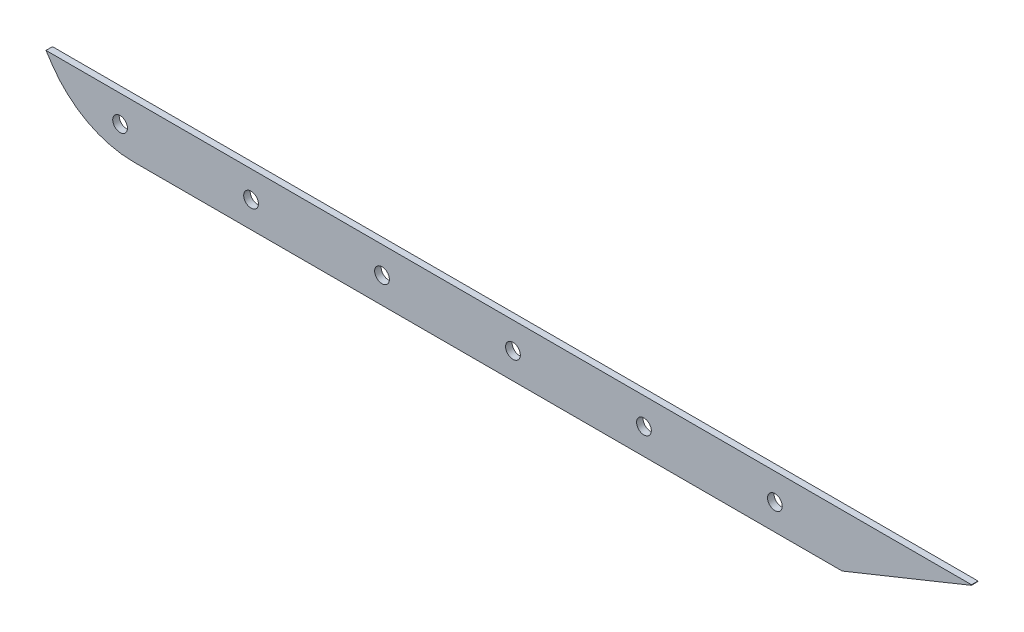
SolidWorks part; units mm, degrees
material "5052-H34"
ref_plane "Front Plane" through (0, 0, 0) normal (0, 0, 1) x (1, 0, 0)
ref_plane "Top Plane" through (0, 0, 0) normal (0, 1, 0) x (1, 0, 0)
ref_plane "Right Plane" through (0, 0, 0) normal (1, 0, 0) x (0, 0, -1)
sketch "Sketch1" plane through (0, 0, 0) normal (0, 0, 1) x (1, 0, 0)
  line L3 (428.1206, 28.9396) -> (0.5404, 28.9396)
  line L6 (-98.8794, 3.851) -> (-31.8794, -96.649)
  line L7 (428.1206, 28.9396) -> (403.1206, -71.149)
  line L9 (403.1206, -71.149) -> (366, -96.649)
  line L10 (-31.8794, -96.649) -> (366, -96.649)
  line L11 (0.5404, 28.9396) -> (-115.6052, 28.9396)
  line L12 (-98.8794, 3.851) -> (-115.6052, 28.9396)
  line L13 (-49.0861, -70.839) -> (403.198, -70.839)
  circle A0 centre (-12.8794, -83.899) radius 3.6
  circle A1 centre (51.1206, -83.899) radius 3.6
  circle A2 centre (115.1206, -83.899) radius 3.6
  circle A3 centre (179.1206, -83.899) radius 3.6
  circle A4 centre (243.1206, -83.899) radius 3.6
  circle A5 centre (307.1206, -83.899) radius 3.6
  point P0 (-48.8794, -71.149)
  point P2 (-31.8794, -96.649)
  point P8 (48, -83.899)
  point P9 (403.1206, -71.149)
  point P23 (-49.0861, -70.839)
  point P26 (403.198, -70.839)
  dimension "D2" = 64
  dimension "D4" = 64
  dimension "D1" = 25.5
  dimension "D3" = 75
  dimension "D5" = 25
  dimension "D6" = 96
  dimension "D7" = 527
  dimension "D8" = 180
  dimension "D9" = 64
  dimension "D10" = 64
  dimension "D11" = 64
  dimension "D12" = 123.69
  dimension "D13" = 12.75
  dimension "D14" = 25.81
  dimension "D15" = 25.81
extrude "Boss-Extrude1" add sketch "Sketch1" along normal blind 3.175 contours L3 L11 L12 L6 L10 L9 L7
extrude "Cut-Extrude1" cut sketch "Sketch1<4>" along normal through all contours A0 | A1 | A2 | A3 | A4 | A5 region at (-12.8794, -83.899, 0)
sketch "Sketch1<4>" plane through (0, 0, 0) normal (0, 0, 1) x (1, 0, 0) same geometry as "Sketch1"
sketch "Sketch2" plane through (0, 0, 0) normal (0, 0, -1) x (-1, 0, 0)
  circle A0 centre (-275.1206, -83.899) radius 6.5
  circle A2 centre (-233.5603, -132.5687) radius 6.5
  circle A3 centre (-192, -83.899) radius 6.5
  circle A4 centre (-128, -83.899) radius 6.5
  circle A5 centre (-64, -83.899) radius 6.5
  circle A6 centre (0, -83.899) radius 6.5
  dimension "D2" = 0
  dimension "D3" = 64
  dimension "D4" = 64
  dimension "D5" = 64
  dimension "D6" = 64
  dimension "D7" = 64
  dimension "D1" = 32
sketch "Sketch5" plane through (0, 0, 0) normal (0, 0, -1) x (-1, 0, 0)
  line L0 (48.8794, -71.149) -> (-14.2353, -96.649)
  line L1 (31.8794, -96.649) -> (-366, -96.649) construction
  line L2 (-14.2353, -96.649) -> (31.8794, -96.649)
  line L3 (31.8794, -96.649) -> (48.8794, -71.149)
  line L6 (-366, -96.649) -> (-403.1206, -71.149)
  line L7 (-403.1206, -71.149) -> (-352, -71.149)
  line L9 (-352, -71.149) -> (-326.5, -96.649)
  line L11 (-366, -96.649) -> (-326.5, -96.649)
  dimension "D1" = 22
  dimension "D2" = 45
extrude "Cut-Extrude2" [suppressed] cut sketch "Sketch5" against normal up to next
sketch "Sketch6" plane through (0, 0, 3.175) normal (0, 0, 1) x (1, 0, 0)
  line L0 (-48.8794, -71.149) -> (14.2353, -96.649)
  line L1 (-31.8794, -96.649) -> (366, -96.649) construction
  line L2 (14.2353, -96.649) -> (-31.8794, -96.649)
  line L3 (-31.8794, -96.649) -> (-48.8794, -71.149)
  dimension "D1" = 158
fillet "Fillet1" radius 48 1 edges at (-31.8794, -96.649, 1.5875)
sketch "Sketch7" plane through (0, 0, 3.175) normal (0, 0, 1) x (1, 0, 0)
  line L0 (403.1206, -71.149) -> (340.0059, -96.649)
  line L1 (-31.8794, -96.649) -> (366, -96.649) construction
  line L2 (340.0059, -96.649) -> (366, -96.649)
  line L3 (366, -96.649) -> (403.1206, -71.149)
  dimension "D1" = 22
extrude "Cut-Extrude3" cut sketch "Sketch7" against normal blind 10
sketch "Sketch9" plane through (0, 0, 0) normal (0, 0, -1) x (-1, 0, 0)
  line L0 (-403.1206, -71.149) -> (48.8794, -71.149)
  line L1 (48.8794, -71.149) -> (48.8794, -114.9143)
  line L2 (48.8794, -114.9143) -> (-403.1206, -114.9143)
  line L3 (-403.1206, -114.9143) -> (-403.1206, -71.149)
extrude "Cut-Extrude4" [suppressed] cut sketch "Sketch9" against normal blind 10
sketch "Sketch10" plane through (0, 0, 3.175) normal (0, 0, 1) x (1, 0, 0)
  line L0 (-49.0861, -70.839) -> (403.198, -70.839) construction
  line L1 (-49.0861, -70.839) -> (403.198, -70.839)
  line L2 (-49.0861, -70.839) -> (-115.6052, 28.9396)
  line L3 (-115.6052, 28.9396) -> (428.1206, 28.9396)
  line L4 (428.1206, 28.9396) -> (403.198, -70.839)
extrude "Cut-Extrude5" cut sketch "Sketch10" against normal blind 10
